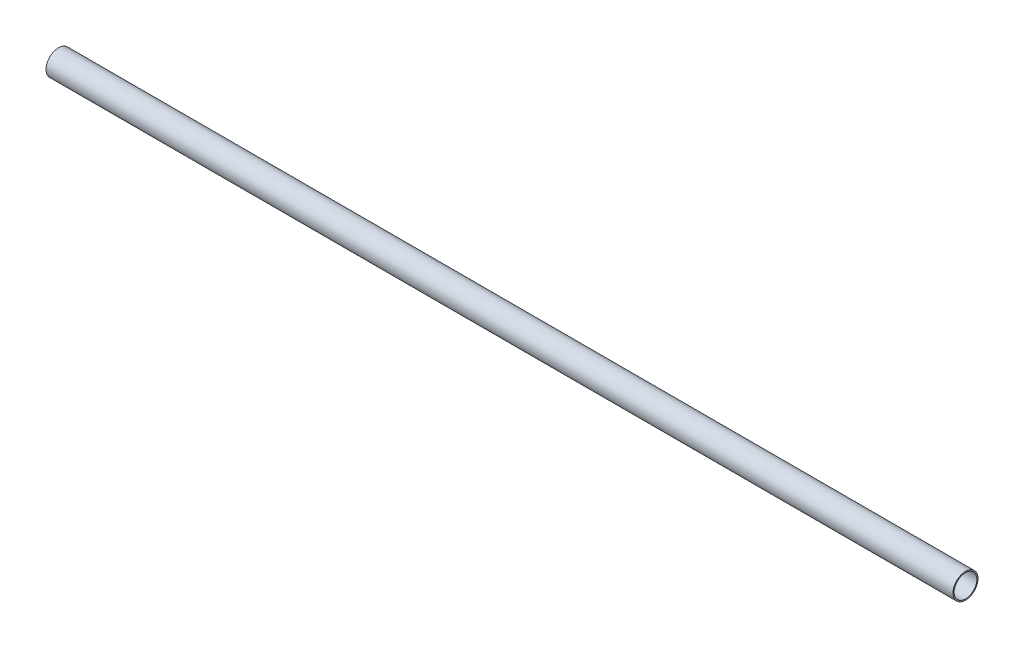
SolidWorks part; units mm, degrees
ref_plane "Front Plane" through (0, 0, 0) normal (0, 0, 1) x (1, 0, 0)
ref_plane "Top Plane" through (0, 0, 0) normal (0, 1, 0) x (1, 0, 0)
ref_plane "Right Plane" through (0, 0, 0) normal (1, 0, 0) x (0, 0, -1)
sketch "Sketch1" plane through (0, 0, 0) normal (1, 0, 0) x (0, 0, -1)
  circle A0 centre (0, 0) radius 9.525
  circle A1 centre (0, 0) radius 8.636
  dimension "D1" = 19.05
  dimension "D2" = 17.272
extrude "Boss-Extrude1" add sketch "Sketch1" along normal up to surface (690.2019 mm away)
equation "\"D1\" = 12.489 - 2 *  ( .25 + 3 / 8 + .312 / 2 ) "
